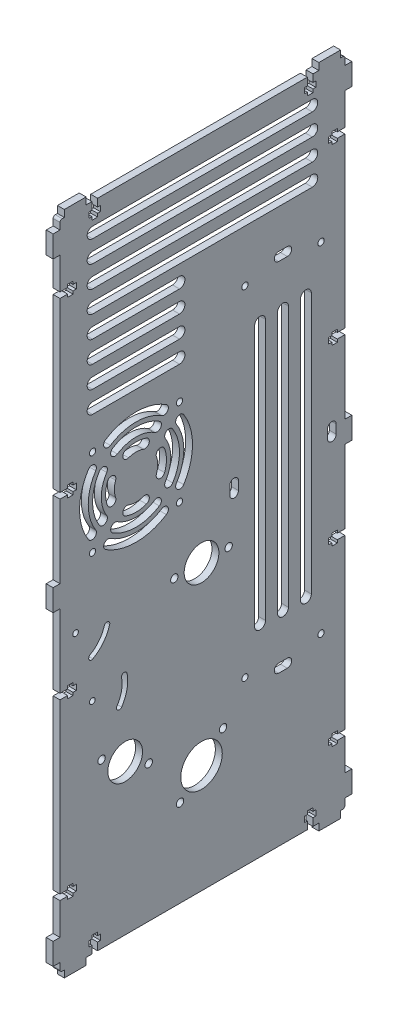
SolidWorks part; units mm, degrees
note: The reader was unsure of these and kept them because the rebuilt part matched: shared geometry of "Sketch28<4>", "Sketch28<5>".
material "MDF"
ref_plane "Front Plane" through (0, 0, 0) normal (0, 0, 1) x (1, 0, 0)
ref_plane "Top Plane" through (0, 0, 0) normal (0, 1, 0) x (1, 0, 0)
ref_plane "Right Plane" through (0, 0, 0) normal (1, 0, 0) x (0, 0, -1)
sketch "Sketch1" plane through (0, 0, 0) normal (1, 0, 0) x (0, 0, -1)
  line L0 (-35.1442, -61.6918) -> (0, 0) construction
  line L1 (-65.1442, 169.2062) -> (66, 169.2062)
  line L2 (-65.1442, 169.2062) -> (-65.1442, -130.7938)
  line L3 (-65.1442, -130.7938) -> (66, -130.7938)
  line L4 (66, 169.2062) -> (66, -130.7938)
  line L5 (6.1803, 19.0211) -> (-6.1803, -19.0211) construction
  line L6 (-19.0211, 6.1803) -> (19.0211, -6.1803) construction
  line L7 (0, 20) -> (0, -20) construction
  line L8 (-33.7459, -51.7901) -> (3.3559, -57.0296) construction
  line L9 (-42.6928, -68.2508) -> (-18.1165, -96.5352) construction
  line L10 (0, 0) -> (-7.8305, -55.4498) construction
  line L11 (-35.1442, -61.6918) -> (0, -80.7938) construction
  line L12 (-42.6928, -68.2508) -> (-35.1442, -61.6918) construction
  line L13 (-35.1442, -61.6918) -> (-33.7459, -51.7901) construction
  line L14 (-49.4048, -50.4805) -> (-6.0061, 4.7219) construction
  line L15 (7.1247, -2.7584) -> (-18.2278, -68.2412) construction
  line L16 (-7.4817, 1.547) -> (-23.5028, -75.934) construction
  line L17 (23.5028, -75.934) -> (7.4817, 1.547) construction
  circle A0 centre (0, 0) radius 20 construction
  circle A1 centre (0, 0) radius 13.5 construction
  circle A2 centre (0, 0) radius 46 construction
  circle A3 centre (-35.1442, -61.6918) radius 18.14 construction
  circle A4 centre (0, -80.7938) radius 24 construction
  circle A5 centre (-35.1442, -61.6918) radius 10 construction
  circle A6 centre (0, 0) radius 7.64 construction
  point P11 (0, 0)
  point P14 (0, 0)
  point P26 (-6.4322, -45.5481)
  dimension "D1" = 40
  dimension "D2" = 27
  dimension "D6" = 92
  dimension "D7" = 36.28
  dimension "D11" = 48
  dimension "D12" = 20
  dimension "D15" = 15.28
  dimension "D3" = 30
  dimension "D4" = 66
  dimension "D5" = 40
  dimension "D8" = 71
  dimension "D9" = 300
  dimension "D10" = 50
  dimension "D13" = 18
  dimension "D14" = 10
extrude "Transmission" add sketch "Sketch1" along normal mid plane 3.175
hole_wizard "MotorClearanceHoles" [suppressed] positions "Sketch2" profile "Sketch3" hole size "M3" standard "ANSI Metric"
sketch "Sketch2" plane through (1.5875, 0, 0) normal (1, 0, 0) x (0, 0, -1)
  point P16 (6.1803, 19.0211)
  point P19 (-19.0211, 6.1803)
  point P22 (-6.1803, -19.0211)
  point P25 (19.0211, -6.1803)
sketch "Sketch3" plane through (1.5, 19.0211, -6.1803) normal (0, 1, 0) x (0, 0, -1)
  line L0 (0, 0) -> (0, 3)
  line L1 (0, 3) -> (1.7, 3)
  line L2 (1.7, 3) -> (1.7, 0.021)
  line L3 (1.7, 0.021) -> (1.725, 0)
  line L5 (1.725, 0) -> (0, 0)
  line L6 (-1.7, 0.021) -> (-1.725, 0) construction
  line L11 (0, -6.35) -> (0, 107.95) construction
  dimension "Thru Hole Dia." = 3.4
  dimension "Thru Hole Depth" = 3
  dimension "Near C'Sink Dia." = 3.45
  dimension "Near C'Sink Angle" = 100
sketch "Sketch16" plane through (0, 0, 0) normal (1, 0, 0) x (0, 0, -1)
  line L0 (33.4127, 17.0246) -> (0, 0) construction
  line L1 (35.5554, 29.3396) -> (44.6352, 11.5195)
  line L2 (35.5554, 29.3396) -> (22.1903, 22.5298)
  line L3 (22.1903, 22.5298) -> (31.2701, 4.7096)
  line L4 (44.6352, 11.5195) -> (31.2701, 4.7096)
  line L5 (35.5554, 29.3396) -> (31.2701, 4.7096) construction
  line L6 (22.1903, 22.5298) -> (44.6352, 11.5195) construction
  line L7 (6.1803, 19.0211) -> (-6.1803, -19.0211) construction
  point P0 (33.4127, 17.0246)
  dimension "D1" = 20
  dimension "D2" = 15
  dimension "D3" = 37.5
  dimension "D4" = 45
extrude "MotorWiresCutout" [suppressed] cut sketch "Sketch16" against normal through all both and the other way through all contours L4 L3 L2 L1
sketch "MotorDriverHolesSketch" plane through (0, 0, 0) normal (1, 0, 0) x (0, 0, -1)
  line L0 (-1000, 0) -> (49000, 0) construction
  line L1 (20, -23) -> (-20, -23) construction
  line L2 (20, -23) -> (20, 15) construction
  line L3 (20, 15) -> (-20, 15) construction
  line L4 (-20, -23) -> (-20, 15) construction
  dimension "D1" = 20
  dimension "D2" = 20
  dimension "D3" = 23
  dimension "D4" = 15
hole_wizard "MotorDriverHoles" [suppressed] positions "Sketch14" profile "Sketch15" hole size "M2.5" standard "ANSI Metric"
sketch "Sketch14" plane through (1.5875, 0, 0) normal (1, 0, 0) x (0, 0, -1)
  point P3 (-20, -23)
  point P6 (-20, 15)
  point P9 (20, 15)
  point P14 (20, -23)
sketch "Sketch15" plane through (1.5, -23, 20) normal (0, 1, 0) x (0, 0, -1)
  line L0 (0, 0) -> (0, 3)
  line L1 (0, 3) -> (1.45, 3)
  line L2 (1.45, 3) -> (1.45, 0)
  line L5 (1.45, 0) -> (0, 0)
  line L11 (0, -6.35) -> (0, 107.95) construction
  dimension "Thru Hole Dia." = 2.9
  dimension "Thru Hole Depth" = 3
sketch "Sketch4" plane through (0, 0, 0) normal (1, 0, 0) x (0, 0, -1)
  line L0 (0, 20) -> (0, -20) construction
  line L1 (-1000, 0) -> (49000, 0) construction
  line L2 (-3.8349, 43.8326) -> (0, 0) construction
  line L3 (-19.0211, 6.1803) -> (19.0211, -6.1803) construction
  line L4 (18.5952, 39.8775) -> (0, 0) construction
  line L5 (0, 0) -> (7.9878, 45.3012) construction
  line L6 (6.1803, 19.0211) -> (-6.1803, -19.0211) construction
  line L7 (0, 0) -> (7.6405, 43.3315) construction
  arc A8 (15.2143, 32.6271) -> (-3.1376, 35.863) centre (0, 0) ccw construction
  arc A9 (16.0595, 34.4397) -> (-3.3119, 37.8554) centre (0, 0) ccw
  arc A10 (14.369, 30.8145) -> (-2.9633, 33.8706) centre (0, 0) ccw
  arc A11 (14.369, 30.8145) -> (16.0595, 34.4397) centre (15.2143, 32.6271) ccw
  arc A12 (-3.3119, 37.8554) -> (-2.9633, 33.8706) centre (-3.1376, 35.863) ccw
  arc A13 (18.5952, 39.8775) -> (-3.8349, 43.8326) centre (0, 0) ccw construction
  arc A14 (19.4404, 41.6902) -> (-4.0092, 45.825) centre (0, 0) ccw
  arc A15 (17.75, 38.0649) -> (-3.6605, 41.8402) centre (0, 0) ccw
  arc A16 (17.75, 38.0649) -> (19.4404, 41.6902) centre (18.5952, 39.8775) ccw
  arc A17 (-4.0092, 45.825) -> (-3.6605, 41.8402) centre (-3.8349, 43.8326) ccw
  arc A18 (11.8333, 25.3766) -> (-2.4404, 27.8935) centre (0, 0) ccw construction
  arc A19 (12.6785, 27.1892) -> (-2.6147, 29.8858) centre (0, 0) ccw
  arc A20 (10.9881, 23.564) -> (-2.266, 25.9011) centre (0, 0) ccw
  arc A21 (10.9881, 23.564) -> (12.6785, 27.1892) centre (11.8333, 25.3766) ccw
  arc A22 (-2.6147, 29.8858) -> (-2.266, 25.9011) centre (-2.4404, 27.8935) ccw
  circle A23 centre (0, 0) radius 46 construction
  point P6 (6.2513, 35.4531)
  point P11 (7.6405, 43.3315)
  point P24 (4.8621, 27.5746)
  dimension "D2" = 4
  dimension "D3" = 4
  dimension "D4" = 4
  dimension "D5" = 4
  dimension "D7" = 30
  dimension "D8" = 80
extrude "Vents" [suppressed] cut sketch "Sketch4" against normal through all both and the other way through all
pattern_circular "VentPattern" [suppressed] count 4 over 360
hole_wizard "M3x0.5 Tapped Hole1" [suppressed] positions "Sketch6" profile "Sketch8" tap size "M3x0.5" standard "ANSI Metric"
sketch "Sketch6" plane through (1.5875, 0, 0) normal (1, 0, 0) x (0, 0, -1)
  circle A0 centre (0, 0) radius 20 construction
  point P0 (0, 20)
  point P3 (0, -20)
  point P6 (20, 0)
  point P10 (-20, 0)
sketch "Sketch8" plane through (1.5, 20, 0) normal (0, 1, 0) x (0, 0, -1)
  line L0 (0, 0) -> (0, 3)
  line L1 (0, 3) -> (1.25, 3)
  line L2 (1.25, 3) -> (1.25, 0)
  line L5 (1.25, 0) -> (0, 0)
  line L11 (0, -6.35) -> (0, 107.95) construction
  dimension "Thru Tap Drill Dia." = 2.5
  dimension "Thru Tap Drill Depth" = 3
cosmetic thread "Hole Thread1" [suppressed] parameters "D2"=3
cosmetic thread "Hole Thread2" [suppressed] parameters "D2"=3
cosmetic thread "Hole Thread3" [suppressed] parameters "D2"=3
cosmetic thread "Hole Thread4" [suppressed] parameters "D2"=3
sketch "Sketch9" plane through (0, 0, 0) normal (1, 0, 0) x (0, 0, -1)
  line L0 (-46.0055, -55.5045) -> (-24.283, -67.8792) construction
  line L1 (-35.1442, -61.6918) -> (0, 0) construction
  line L2 (-9.8995, -90.6933) -> (9.8995, -70.8943) construction
  line L3 (-1000, 0) -> (49000, 0) construction
  line L4 (-12.5, 0) -> (12.5, 0) construction
  circle A0 centre (-35.1442, -61.6918) radius 7.9875
  circle A1 centre (0, -80.7938) radius 9.55
  circle A2 centre (0, 0) radius 7.9875
  point P6 (-35.1442, -61.6918)
  point P14 (0, -80.7938)
  point P24 (0, 0)
  dimension "D1" = 15.975
  dimension "D3" = 19.1
  dimension "D2" = 25
  dimension "D4" = 45
  dimension "D5" = 28
  dimension "D6" = 25
extrude "BearingHoles" cut sketch "Sketch9" against normal through all both and the other way through all
hole_wizard "BearingCoverHoles" positions "Sketch10" profile "Sketch11" hole size "M3" standard "ANSI Metric" end condition through all
sketch "Sketch10" plane through (1.5875, 0, 0) normal (1, 0, 0) x (0, 0, -1)
  point P0 (-46.0055, -55.5045)
  point P3 (-24.283, -67.8792)
  point P6 (9.8995, -70.8943)
  point P9 (-9.8995, -90.6933)
  point P12 (-12.5, 0)
  point P15 (12.5, 0)
sketch "Sketch11" plane through (1.5875, -55.5045, 46.0055) normal (0, 1, 0) x (0, 0, -1)
  line L0 (0, 0) -> (0, 3.175)
  line L1 (0, 3.175) -> (1.7, 3.175)
  line L2 (1.7, 3.175) -> (1.7, 0)
  line L5 (1.7, 0) -> (0, 0)
  line L11 (0, -6.35) -> (0, 107.95) construction
  dimension "Thru Hole Dia." = 3.4
  dimension "Thru Hole Depth" = 3.175
sketch "TensionerSketch" plane through (0, 0, 0) normal (1, 0, 0) x (0, 0, -1)
  line L0 (-46.1798, -8.3552) -> (-57.972, 0.9154) construction
  line L1 (-46.1798, -8.3552) -> (-32.8154, -18.862) construction
  line L2 (-32.8154, -18.862) -> (-27.7055, -22.8793) construction
  line L3 (-49.4048, -50.4805) -> (-6.0061, 4.7219) construction
  line L4 (-27.7055, -22.8793) -> (-24.5609, -25.3515) construction
  line L5 (-57.972, 0.9154) -> (-50.6252, -12.1622) construction
  line L6 (-57.972, 0.9154) -> (-43.5297, -3.1369) construction
  line L7 (-50.2569, -30.0051) -> (-35.5676, -33.0424) construction
  line L8 (-35.5676, -33.0424) -> (-18.9198, -36.4848) construction
  line L10 (-15.4923, -37.1935) -> (-8.6373, -38.6109) construction
  line L11 (-50.2569, -30.0051) -> (-35.5234, -27.1899) construction
  line L12 (-7.4817, 1.547) -> (-23.5028, -75.934) construction
  line L13 (-50.2569, -30.0051) -> (-37.8481, -38.4325) construction
  circle A0 centre (-46.1798, -8.3552) radius 1.3 construction
  circle A1 centre (-57.972, 0.9154) radius 1.3
  circle A2 centre (-32.8154, -18.862) radius 10.5 construction
  arc A3 (-43.5297, -3.1369) -> (-50.6252, -12.1622) centre (-57.972, 0.9154) cw construction
  arc A4 (-49.9885, -13.2956) -> (-42.2781, -3.4881) centre (-57.972, 0.9154) ccw
  arc A5 (-51.2619, -11.0288) -> (-44.7814, -2.7857) centre (-57.972, 0.9154) ccw
  arc A6 (-51.2619, -11.0288) -> (-49.9885, -13.2956) centre (-50.6252, -12.1622) ccw
  arc A7 (-42.2781, -3.4881) -> (-44.7814, -2.7857) centre (-43.5297, -3.1369) ccw
  circle A8 centre (-18.9198, -36.4848) radius 10.5 construction
  circle A9 centre (-50.2569, -30.0051) radius 1.3
  arc A10 (-35.5234, -27.1899) -> (-37.8481, -38.4325) centre (-50.2569, -30.0051) cw construction
  arc A11 (-36.7727, -39.1629) -> (-34.2465, -26.9459) centre (-50.2569, -30.0051) ccw
  arc A12 (-38.9235, -37.7022) -> (-36.8003, -27.4339) centre (-50.2569, -30.0051) ccw
  arc A13 (-38.9235, -37.7022) -> (-36.7727, -39.1629) centre (-37.8481, -38.4325) ccw
  arc A14 (-34.2465, -26.9459) -> (-36.8003, -27.4339) centre (-35.5234, -27.1899) ccw
  point P11 (-24.5609, -25.3515)
  point P12 (-46.1798, -8.3552)
  point P25 (-8.6373, -38.6109)
  point P33 (-35.5676, -33.0424)
  dimension "D2" = 2.6
  dimension "D3" = 21
  dimension "D6" = 2.6
  dimension "D9" = 2.6
  dimension "D10" = 2.6
  dimension "D1" = 15
  dimension "D4" = 17
  dimension "D5" = 4
  dimension "D7" = 45
  dimension "D8" = 7
  dimension "D11" = 45
extrude "Tensioner" cut sketch "TensionerSketch" against normal through all both and the other way through all contours A0
sketch "UBEC" plane through (1.5875, 0, 0) normal (1, 0, 0) x (0, 0, -1)
  line L1 (-47.5326, 111.4637) -> (1.4674, 111.4637) construction
  line L2 (-47.5326, 111.4637) -> (-47.5326, 53.4637) construction
  line L3 (-47.5326, 53.4637) -> (1.4674, 53.4637) construction
  line L4 (1.4674, 111.4637) -> (1.4674, 53.4637) construction
  point P0 (-47.5326, 111.4637)
  point P1 (1.4674, 53.4637)
  point P2 (-47.5326, 53.4637)
  point P3 (1.4674, 111.4637)
  point P20 (-47.5326, 111.4637)
  point P22 (1.4674, 111.4637)
  point P24 (-47.5326, 53.4637)
  point P26 (1.4674, 53.4637)
  dimension "D1" = 58
  dimension "D2" = 49
sketch "FanSketch" plane through (1.5875, 0, 0) normal (1, 0, 0) x (0, 0, -1)
  line L1 (-50.1442, 69.2062) -> (-10.1442, 69.2062) construction
  line L2 (-50.1442, 69.2062) -> (-50.1442, 29.2062) construction
  line L3 (-50.1442, 29.2062) -> (-10.1442, 29.2062) construction
  line L4 (-10.1442, 69.2062) -> (-10.1442, 29.2062) construction
  line L5 (-65.1442, 169.2062) -> (-65.1442, -130.7938) construction
  line L6 (-65.1442, -130.7938) -> (66, -130.7938) construction
  point P0 (-50.1442, 69.2062)
  point P1 (-10.1442, 29.2062)
  point P2 (-50.1442, 29.2062)
  point P3 (-10.1442, 69.2062)
  point P14 (-50.1442, 69.2062)
  point P16 (-10.1442, 69.2062)
  point P18 (-10.1442, 29.2062)
  point P20 (-50.1442, 29.2062)
  dimension "D1" = 40
  dimension "D2" = 15
  dimension "D3" = 160
hole_wizard "M2.5ClearanceHoles for Fan" positions "FanSketch" profile "Sketch20" hole size "M2.5" standard "ANSI Metric" end condition through all
sketch "Sketch20" plane through (1.5875, 29.2062, 50.1442) normal (0, 1, 0) x (0, 0, -1)
  line L0 (0, 0) -> (0, 3.175)
  line L1 (0, 3.175) -> (1.45, 3.175)
  line L2 (1.45, 3.175) -> (1.45, 0)
  line L5 (1.45, 0) -> (0, 0)
  line L11 (0, -6.35) -> (0, 107.95) construction
  dimension "Thru Hole Dia." = 2.9
  dimension "Thru Hole Depth" = 3.175
sketch "Sketch21" plane through (1.5875, 0, 0) normal (1, 0, 0) x (0, 0, -1)
  line L0 (-50.1442, 69.2062) -> (-10.1442, 29.2062) construction
  line L1 (-34.2485, 60.4825) -> (-30.1442, 49.2062) construction
  line L2 (-30.1442, 49.2062) -> (-26.04, 60.4825) construction
  line L3 (-30.1442, 73.2062) -> (-30.1442, 49.2062) construction
  line L4 (-30.1442, 49.2062) -> (-17.249, 69.4476) construction
  line L5 (-30.1442, 49.2062) -> (-43.0394, 69.4476) construction
  line L6 (-30.1442, 49.2062) -> (-10.1442, 49.2062) construction
  line L7 (-10.1442, 69.2062) -> (-10.1442, 29.2062) construction
  arc A1 (-17.249, 69.4476) -> (-43.0394, 69.4476) centre (-30.1442, 49.2062) ccw construction
  arc A2 (-16.1744, 71.1344) -> (-44.114, 71.1344) centre (-30.1442, 49.2062) ccw
  arc A3 (-18.3236, 67.7608) -> (-41.9648, 67.7608) centre (-30.1442, 49.2062) ccw
  arc A4 (-18.3236, 67.7608) -> (-16.1744, 71.1344) centre (-17.249, 69.4476) ccw
  arc A5 (-44.114, 71.1344) -> (-41.9648, 67.7608) centre (-43.0394, 69.4476) ccw
  arc A6 (-20.4728, 64.3873) -> (-39.8156, 64.3873) centre (-30.1442, 49.2062) ccw construction
  arc A7 (-19.3982, 66.0741) -> (-40.8902, 66.0741) centre (-30.1442, 49.2062) ccw
  arc A8 (-21.5474, 62.7005) -> (-38.741, 62.7005) centre (-30.1442, 49.2062) ccw
  arc A9 (-21.5474, 62.7005) -> (-19.3982, 66.0741) centre (-20.4728, 64.3873) ccw
  arc A10 (-40.8902, 66.0741) -> (-38.741, 62.7005) centre (-39.8156, 64.3873) ccw
  arc A11 (-26.04, 60.4825) -> (-34.2485, 60.4825) centre (-30.1442, 49.2062) ccw construction
  arc A12 (-25.3559, 62.3619) -> (-34.9325, 62.3619) centre (-30.1442, 49.2062) ccw
  arc A13 (-26.724, 58.6032) -> (-33.5644, 58.6032) centre (-30.1442, 49.2062) ccw
  arc A14 (-26.724, 58.6032) -> (-25.3559, 62.3619) centre (-26.04, 60.4825) ccw
  arc A15 (-34.9325, 62.3619) -> (-33.5644, 58.6032) centre (-34.2485, 60.4825) ccw
  arc A16 (-28.0921, 54.8444) -> (-32.1963, 54.8444) centre (-30.1442, 49.2062) ccw construction
  arc A17 (-27.4081, 56.7238) -> (-32.8804, 56.7238) centre (-30.1442, 49.2062) ccw construction
  arc A18 (-28.7761, 52.965) -> (-31.5123, 52.965) centre (-30.1442, 49.2062) ccw construction
  arc A19 (-28.7761, 52.965) -> (-27.4081, 56.7238) centre (-28.0921, 54.8444) ccw construction
  arc A20 (-32.8804, 56.7238) -> (-31.5123, 52.965) centre (-32.1963, 54.8444) ccw construction
  point P13 (-30.1442, 73.2062)
  point P23 (-30.1442, 67.2062)
  point P28 (-30.1442, 61.2062)
  point P37 (-30.1442, 55.2062)
  dimension "D1" = 65
  dimension "D2" = 2
  dimension "D4" = 24
  dimension "D5" = 2
  dimension "D6" = 2
  dimension "D7" = 2
  dimension "D8" = 2
  dimension "D9" = 40
  dimension "D11" = 2
  dimension "D3" = 90
extrude "Cut-Extrude1" cut sketch "Sketch21" against normal through all both and the other way through all
pattern_circular "CirPattern1" count 4 over 360 about axis through (0, 49.2062, 30.1442) along (1, 0, 0) of "Cut-Extrude1"
sketch "Sketch22" plane through (0, 0, 0) normal (1, 0, 0) x (0, 0, -1)
  line L0 (66, -130.7938) -> (66, 169.2062) construction
  line L1 (20, 100.3062) -> (55, 100.3062) construction
  line L2 (20, 100.3062) -> (20, -55.7938) construction
  line L3 (20, -55.7938) -> (55, -55.7938) construction
  line L4 (55, 100.3062) -> (55, -55.7938) construction
  line L5 (-65.1442, -130.7938) -> (66, -130.7938) construction
  line L6 (15, 24.2562) -> (15, 20.2562) construction
  line L7 (17, 24.2562) -> (17, 20.2562)
  line L8 (13, 24.2562) -> (13, 20.2562)
  line L9 (60, 24.2562) -> (60, 20.2562) construction
  line L10 (62, 24.2562) -> (62, 20.2562)
  line L11 (58, 24.2562) -> (58, 20.2562)
  line L12 (35.5, 104.3062) -> (39.5, 104.3062) construction
  line L13 (35.5, 106.3062) -> (39.5, 106.3062)
  line L14 (35.5, 102.3062) -> (39.5, 102.3062)
  line L15 (35.5, -59.7938) -> (39.5, -59.7938) construction
  line L16 (35.5, -57.7938) -> (39.5, -57.7938)
  line L17 (35.5, -61.7938) -> (39.5, -61.7938)
  arc A0 (17, 24.2562) -> (13, 24.2562) centre (15, 24.2562) ccw
  arc A1 (13, 20.2562) -> (17, 20.2562) centre (15, 20.2562) ccw
  arc A2 (62, 24.2562) -> (58, 24.2562) centre (60, 24.2562) ccw
  arc A3 (58, 20.2562) -> (62, 20.2562) centre (60, 20.2562) ccw
  arc A4 (35.5, 106.3062) -> (35.5, 102.3062) centre (35.5, 104.3062) ccw
  arc A5 (39.5, 102.3062) -> (39.5, 106.3062) centre (39.5, 104.3062) ccw
  arc A6 (35.5, -57.7938) -> (35.5, -61.7938) centre (35.5, -59.7938) ccw
  arc A7 (39.5, -61.7938) -> (39.5, -57.7938) centre (39.5, -59.7938) ccw
  point P10 (15, 22.2562)
  point P15 (60, 22.2562)
  point P22 (37.5, 104.3062)
  point P29 (37.5, -59.7938)
  point P37 (20, 22.2562)
  point P39 (37.5, -57.7938)
  point P41 (37.5, 100.3062)
  dimension "D5" = 4
  dimension "D1" = 35
  dimension "D2" = 156.1
  dimension "D3" = 11
  dimension "D4" = 75
  dimension "D9" = 2
  dimension "D10" = 2
extrude "Cut-Extrude2" cut sketch "Sketch22" against normal through all both and the other way through all
hole_wizard "M2.5 Clearance Hole1" positions "Sketch23" profile "Sketch24" hole size "M2.5" standard "ANSI Metric" end condition through all
sketch "Sketch23" plane through (1.5875, 0, 0) normal (1, 0, 0) x (0, 0, -1)
  point P0 (20, 100.3062)
  point P3 (55, 100.3062)
  point P6 (55, -55.7938)
  point P9 (20, -55.7938)
sketch "Sketch24" plane through (1.5875, 100.3062, -20) normal (0, 1, 0) x (0, 0, -1)
  line L0 (0, 0) -> (0, 3.175)
  line L1 (0, 3.175) -> (1.45, 3.175)
  line L2 (1.45, 3.175) -> (1.45, 0)
  line L5 (1.45, 0) -> (0, 0)
  line L11 (0, -6.35) -> (0, 107.95) construction
  dimension "Thru Hole Dia." = 2.9
  dimension "Thru Hole Depth" = 3.175
sketch "Sketch25" plane through (1.5875, 0, 0) normal (1, 0, 0) x (0, 0, -1)
  line L0 (-65.1442, 169.2062) -> (-65.1442, -130.7938) construction
  line L1 (-65.1442, 165.2062) -> (-68.3192, 165.2062)
  line L2 (-65.1442, 165.2062) -> (-65.1442, 155.2062)
  line L3 (-65.1442, 155.2062) -> (-68.3192, 155.2062)
  line L4 (-68.3192, 165.2062) -> (-68.3192, 155.2062)
  line L5 (66, 169.2062) -> (-65.1442, 169.2062) construction
  line L6 (-65.1442, -130.7938) -> (66, -130.7938) construction
  line L7 (-68.3192, 24.2062) -> (-65.1442, 24.2062)
  line L8 (-68.3192, 24.2062) -> (-68.3192, 14.2062)
  line L9 (-68.3192, 14.2062) -> (-65.1442, 14.2062)
  line L10 (-65.1442, 24.2062) -> (-65.1442, 14.2062)
  line L11 (-68.3192, -116.7938) -> (-65.1442, -116.7938)
  line L12 (-68.3192, -116.7938) -> (-68.3192, -126.7938)
  line L13 (-68.3192, -126.7938) -> (-65.1442, -126.7938)
  line L14 (-65.1442, -116.7938) -> (-65.1442, -126.7938)
  point P19 (-65.1442, 19.2062)
  point P20 (-65.1442, 19.2062)
  dimension "D1" = 3.175
  dimension "D2" = 10
  dimension "D3" = 4
  dimension "D4" = 4
extrude "Boss-Extrude1" add sketch "Sketch25" against normal up to surface (3.175 mm away) up to face at (-1.5875, 100.3062, -21.45)
sketch "Sketch26" plane through (1.5875, 0, 0) normal (1, 0, 0) x (0, 0, -1)
  line L0 (-65.1442, 155.2062) -> (-65.1442, 24.2062) construction
  line L1 (-65.1442, 140.5062) -> (-57.6442, 140.5062)
  line L2 (-65.1442, 140.5062) -> (-65.1442, 137.9062)
  line L3 (-65.1442, 137.9062) -> (-57.6442, 137.9062)
  line L4 (-57.6442, 140.5062) -> (-57.6442, 137.9062)
  line L5 (-65.1442, 139.2062) -> (-57.6442, 139.2062) construction
  line L6 (-61.6442, 141.8062) -> (-59.1442, 141.8062)
  line L7 (-61.6442, 141.8062) -> (-61.6442, 136.6062)
  line L8 (-61.6442, 136.6062) -> (-59.1442, 136.6062)
  line L9 (-59.1442, 141.8062) -> (-59.1442, 136.6062)
  line L10 (66, 169.2062) -> (-65.1442, 169.2062) construction
  point P10 (-61.6442, 139.2062)
  point P11 (-57.6442, 139.2062)
  dimension "D1" = 5.2
  dimension "D2" = 3.5
  dimension "D3" = 1.5
  dimension "D4" = 2.5
  dimension "D5" = 2.6
  dimension "D6" = 30
extrude "Cut-Extrude3" cut sketch "Sketch26" against normal through all both and the other way through all contours L6 L9 L8 L7 | L1 L4 L3 L2
pattern_linear "LPattern1" count 4 spacing 80 along (0, -1, 0) of "Cut-Extrude3"
ref_plane "Plane1" through (0, 0, -0.4279) normal (0, 0, -1) x (-1, 0, 0)
ref_plane "Plane2" through (0, 19.2062, 0) normal (0, 1, 0) x (1, 0, 0)
mirror "Mirror1" about plane through (0, 0, -0.4279) normal (0, 0, -1) of "Boss-Extrude1", "LPattern1", "Cut-Extrude3"
sketch "Sketch28" plane through (1.5875, 0, 0) normal (1, 0, 0) x (0, 0, -1)
  line L0 (-50.1442, 156.7062) -> (51, 156.7062) construction
  line L1 (-50.1442, 159.2062) -> (51, 159.2062)
  line L2 (-50.1442, 154.2062) -> (51, 154.2062)
  line L3 (-50.1442, 86.7062) -> (-10.1442, 86.7062) construction
  line L4 (-50.1442, 89.2062) -> (-10.1442, 89.2062)
  line L5 (-50.1442, 84.2062) -> (-10.1442, 84.2062)
  line L6 (26.9443, 82.2562) -> (26.9443, -37.7438) construction
  line L7 (29.4443, 82.2562) -> (29.4443, -37.7438)
  line L8 (24.4443, 82.2562) -> (24.4443, -37.7438)
  line L9 (17, 20.2562) -> (17, 24.2562) construction
  line L12 (37.5, 82.2562) -> (37.5, -37.7438) construction
  line L13 (40, 82.2562) -> (40, -37.7438)
  line L14 (35, 82.2562) -> (35, -37.7438)
  line L15 (48.0557, 82.2562) -> (48.0557, -37.7438) construction
  line L16 (50.5557, 82.2562) -> (50.5557, -37.7438)
  line L17 (45.5557, 82.2562) -> (45.5557, -37.7438)
  line L19 (58, 24.2562) -> (58, 20.2562) construction
  line L20 (-30.1442, 86.7062) -> (-30.1442, 49.2062) construction
  line L21 (66, 169.2062) -> (-65.1442, 169.2062) construction
  arc A0 (-50.1442, 159.2062) -> (-50.1442, 154.2062) centre (-50.1442, 156.7062) ccw
  arc A1 (51, 154.2062) -> (51, 159.2062) centre (51, 156.7062) ccw
  arc A2 (-50.1442, 89.2062) -> (-50.1442, 84.2062) centre (-50.1442, 86.7062) ccw
  arc A3 (-10.1442, 84.2062) -> (-10.1442, 89.2062) centre (-10.1442, 86.7062) ccw
  arc A4 (29.4443, 82.2562) -> (24.4443, 82.2562) centre (26.9443, 82.2562) ccw
  arc A5 (24.4443, -37.7438) -> (29.4443, -37.7438) centre (26.9443, -37.7438) ccw
  arc A8 (40, 82.2562) -> (35, 82.2562) centre (37.5, 82.2562) ccw
  arc A9 (35, -37.7438) -> (40, -37.7438) centre (37.5, -37.7438) ccw
  arc A10 (50.5557, 82.2562) -> (45.5557, 82.2562) centre (48.0557, 82.2562) ccw
  arc A11 (45.5557, -37.7438) -> (50.5557, -37.7438) centre (48.0557, -37.7438) ccw
  point P2 (0.4279, 156.7062)
  point P7 (-30.1442, 86.7062)
  point P14 (26.9443, 22.2562)
  point P21 (37.5, 22.2562)
  point P24 (17, 22.2562)
  point P32 (48.0557, 22.2562)
  point P43 (0.4279, 169.2062)
  dimension "D2" = 2.5
  dimension "D6" = 2.5
  dimension "D11" = 2.5
  dimension "D1" = 120
  dimension "D4" = 9.9443
  dimension "D5" = 9.9443
  dimension "D7" = 40
  dimension "D8" = 37.5
  dimension "D9" = 10
  dimension "D3" = 3
extrude "Cut-Extrude4" cut sketch "Sketch28" against normal blind 10 contours L17 A11 L16 A10 | L14 A9 L13 A8 | L8 A5 L7 A4
extrude "Cut-Extrude5" cut sketch "Sketch28<4>" against normal blind 10 contours L5 A3 L4 A2
sketch "Sketch28<4>" plane through (1.5875, 0, 0) normal (1, 0, 0) x (0, 0, -1) same geometry as "Sketch28"
pattern_linear "LPattern2" count 4 spacing 10 along (0, 1, 0) of "Cut-Extrude5"
extrude "Cut-Extrude6" cut sketch "Sketch28<5>" against normal blind 10 contours L2 A1 L1 A0
sketch "Sketch28<5>" plane through (1.5875, 0, 0) normal (1, 0, 0) x (0, 0, -1) same geometry as "Sketch28"
pattern_linear "LPattern3" count 4 spacing 10 along (0, -1, 0) of "Cut-Extrude6"
sketch "Sketch29" plane through (1.5875, 0, 0) normal (1, 0, 0) x (0, 0, -1)
  line L0 (66, 169.2062) -> (-65.1442, 169.2062) construction
  line L1 (-63.1442, 169.2062) -> (-53.1442, 169.2062)
  line L2 (-63.1442, 169.2062) -> (-63.1442, 172.3812)
  line L3 (-63.1442, 172.3812) -> (-53.1442, 172.3812)
  line L4 (-53.1442, 169.2062) -> (-53.1442, 172.3812)
  line L5 (-65.1442, 169.2062) -> (-65.1442, 165.2062) construction
  dimension "D1" = 2
  dimension "D2" = 3.175
  dimension "D3" = 10
extrude "Boss-Extrude2" add sketch "Sketch29" against normal up to surface (3.175 mm away) up to face at (-1.5875, 146.7062, -0.4279)
sketch "Sketch30" plane through (1.5875, 0, 0) normal (1, 0, 0) x (0, 0, -1)
  line L0 (66, 169.2062) -> (-53.1442, 169.2062) construction
  line L1 (-50.4442, 169.2062) -> (-47.8442, 169.2062)
  line L2 (-50.4442, 169.2062) -> (-50.4442, 161.7062)
  line L3 (-50.4442, 161.7062) -> (-47.8442, 161.7062)
  line L4 (-47.8442, 169.2062) -> (-47.8442, 161.7062)
  line L5 (-49.1442, 169.2062) -> (-49.1442, 161.7062) construction
  line L6 (-51.7442, 165.7062) -> (-46.5442, 165.7062)
  line L7 (-51.7442, 165.7062) -> (-51.7442, 163.2062)
  line L8 (-51.7442, 163.2062) -> (-46.5442, 163.2062)
  line L9 (-46.5442, 165.7062) -> (-46.5442, 163.2062)
  line L10 (-65.1442, 169.2062) -> (-65.1442, 165.2062) construction
  point P10 (-49.1442, 163.2062)
  point P11 (-49.1442, 161.7062)
  dimension "D1" = 2.6
  dimension "D2" = 5.2
  dimension "D3" = 2.5
  dimension "D4" = 3.5
  dimension "D5" = 1.5
  dimension "D6" = 16
extrude "Cut-Extrude7" cut sketch "Sketch30" against normal through all both and the other way through all contours L4 L3 L2 L1 | L6 L9 L8 L7
mirror "Mirror2" about plane through (0, 19.2062, 0) normal (0, 1, 0) of "Cut-Extrude7", "Boss-Extrude2" second plane through (0, 0, -0.4279) second plane normal (0, 0, -1)
fillet "Fillet1" radius 1 4 edges at (0, 169.2062, -66) (0, 169.2062, 65.1442) (0, -130.7938, -66) (0, -130.7938, 65.1442)
equation "\"D2@Sketch4\"=\"D1@Sketch4\""
equation "\"D3@Sketch4\"=\"D1@Sketch4\""
equation "\"D4@Sketch4\"=\"D1@Sketch4\""
equation "\"D5@Sketch4\"=\"D1@Sketch4\""
equation "\"D5@Sketch28\"=\"D4@Sketch28\""
equation "\"D7@Sketch22\"=\"D8@Sketch22\""
